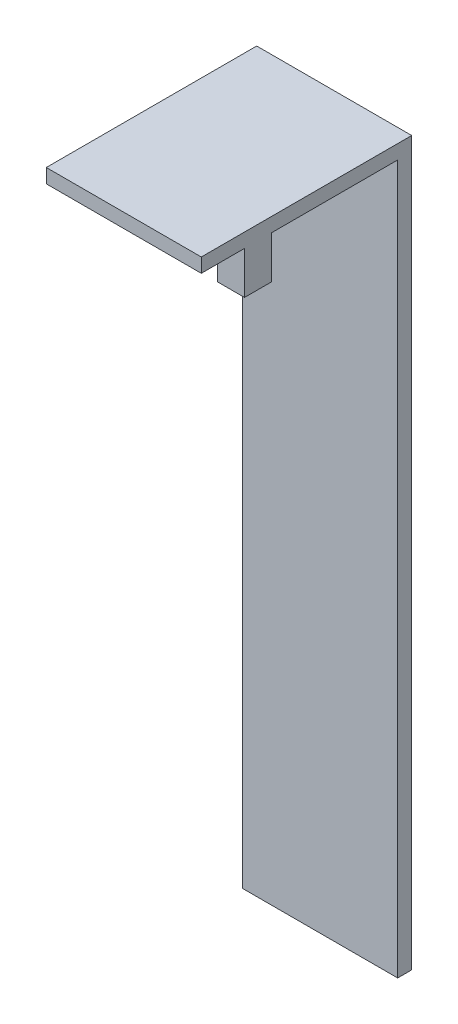
SolidWorks part; units mm, degrees
ref_plane "Front Plane" through (0, 0, 0) normal (0, 0, 1) x (1, 0, 0)
ref_plane "Top Plane" through (0, 0, 0) normal (0, 1, 0) x (1, 0, 0)
ref_plane "Right Plane" through (0, 0, 0) normal (1, 0, 0) x (0, 0, -1)
sketch "Sketch1" plane through (0, 0, 0) normal (0, 1, 0) x (1, 0, 0)
  line L0 (-5.4697, -4.95) -> (-5.4698, 0)
  line L1 (-5.4698, 4.95) -> (5.4698, 4.95)
  line L2 (-5.4698, 4.95) -> (-5.4697, -4.95)
  line L3 (-5.4697, -4.95) -> (5.4698, -4.95)
  line L4 (5.4698, 4.95) -> (5.4698, -4.95)
  line L5 (-5.4698, 4.95) -> (5.4698, -4.95) construction
  line L6 (-5.4697, -4.95) -> (5.4698, 4.95) construction
  line L7 (-5.4698, 0) -> (-5.4698, -1.9)
  line L8 (-5.4698, -1.9) -> (-3.5698, -1.9)
  line L9 (-3.5698, -1.9) -> (-3.5698, 0)
  line L10 (0, -4.95) -> (0, -3.581)
  line L11 (3.5697, 0) -> (5.4697, 0)
  line L12 (3.5697, -1.9) -> (3.5697, 0)
  line L13 (5.4697, -1.9) -> (3.5697, -1.9)
  line L14 (-5.4698, 4.95) -> (-5.4698, 9.9)
  line L15 (-5.4698, 9.9) -> (5.4698, 9.9)
  line L16 (5.4698, 9.9) -> (5.4698, 4.95)
  line L17 (5.4698, 9.9) -> (5.4698, 7.92)
  line L18 (5.4698, 9.9) -> (5.4698, 8.91)
  line L19 (-5.4698, 7.92) -> (-5.4698, 9.9)
  line L20 (-5.4697, -4.95) -> (-5.4698, 0)
  line L21 (-3.5698, 0) -> (-5.4698, 0)
  line L22 (5.4698, 8.91) -> (-5.4698, 8.91)
  line L23 (-5.4698, 8.91) -> (-5.4698, 9.9)
  line L24 (5.4697, 0) -> (5.4697, -1.9)
  point P0 (0, 0)
  dimension "D1" = 4.95
extrude "Boss-Extrude1" add sketch "Sketch1" along normal blind 1 contours L21 L9 L8 L0 L3 L4 L13 L12 L11 L1 L2 | L17 L22 L14 L1 L16 | L22 L16 L15 L19 | L13 L4 L11 L12 | L9 L21 L2 L8 region at (0, 0, -0.0679) region at (-4.5198, 0, 0.95) region at (0, 0, -6.93) region at (4.5197, 0, 0.95) region at (0, 0, -9.405)
extrude "Boss-Extrude2" add sketch "Sketch1<3>" against normal blind 3 contours L9 L21 L2 L8 | L13 L4 L11 L12 region at (-4.5198, 0, 0.95) region at (4.5197, 0, 0.95)
sketch "Sketch1<3>" plane through (0, 0, 0) normal (0, 1, 0) x (1, 0, 0) same geometry as "Sketch1"
extrude "Boss-Extrude3" add sketch "Sketch1<4>" against normal blind 50 contours L22 L16 L15 L19 region at (0, 0, -9.405)
sketch "Sketch1<4>" plane through (0, 0, 0) normal (0, 1, 0) x (1, 0, 0) same geometry as "Sketch1"
